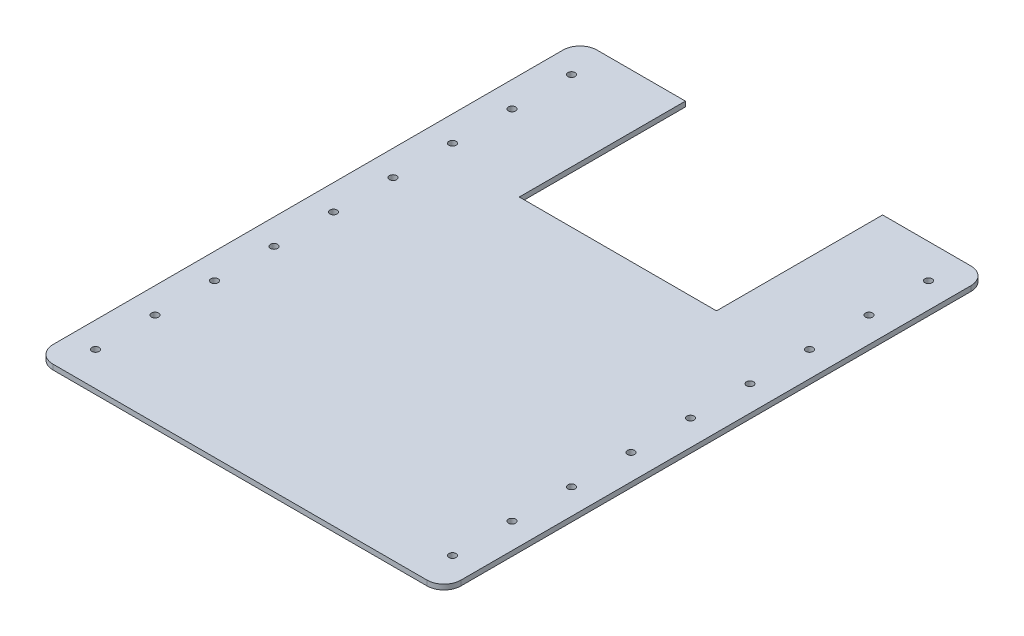
SolidWorks part; units mm, degrees
material "Thornel Mat VMA"
ref_plane "前视基准面" through (0, 0, 0) normal (0, 0, 1) x (1, 0, 0)
ref_plane "上视基准面" through (0, 0, 0) normal (0, 1, 0) x (1, 0, 0)
ref_plane "右视基准面" through (0, 0, 0) normal (1, 0, 0) x (0, 0, -1)
sketch "草图1" plane through (0, 0, 0) normal (0, 1, 0) x (1, 0, 0)
  line L1 (-120, 160) -> (120, 160)
  line L2 (-120, 160) -> (-120, -160)
  line L3 (-120, -160) -> (120, -160)
  line L4 (120, 160) -> (120, -160)
  line L5 (-120, 160) -> (120, -160) construction
  line L6 (-120, -160) -> (120, 160) construction
  point P0 (0, 0)
  dimension "D1" = 320
  dimension "D2" = 240
extrude "凸台-拉伸1" add sketch "草图1" along normal blind 3
fillet "圆角1" radius 10 4 edges at (-120, 1.5, -160) (120, 1.5, -160) (120, 1.5, 160) (-120, 1.5, 160)
sketch "草图2" plane through (0, 3, 0) normal (0, 1, 0) x (1, 0, 0)
  line L0 (-105, -833.0003) -> (-105, 49166.9997) construction
  line L1 (-105, 140) -> (-105, 105) construction
  line L2 (110, 160) -> (-110, 160) construction
  line L3 (0, 0) -> (0, -103.271) construction
  line L4 (105, 140) -> (105, 105) construction
  circle A0 centre (-105, 140) radius 2.1
  circle A1 centre (-105, 105) radius 2.1
  circle A2 centre (-105, 70) radius 2.1
  circle A3 centre (-105, 35) radius 2.1
  circle A4 centre (-105, 0) radius 2.1
  circle A5 centre (-105, -35) radius 2.1
  circle A6 centre (-105, -70) radius 2.1
  circle A7 centre (-105, -105) radius 2.1
  circle A8 centre (-105, -140) radius 2.1
  circle A9 centre (105, -140) radius 2.1
  circle A10 centre (105, -105) radius 2.1
  circle A11 centre (105, -70) radius 2.1
  circle A12 centre (105, -35) radius 2.1
  circle A13 centre (105, 0) radius 2.1
  circle A14 centre (105, 35) radius 2.1
  circle A15 centre (105, 70) radius 2.1
  circle A16 centre (105, 105) radius 2.1
  circle A17 centre (105, 140) radius 2.1
  dimension "D1" = 4.2
  dimension "D2" = 20
  dimension "D3" = 15
  dimension "D5" = 35
  dimension "D4" = 9
extrude "切除-拉伸1" cut sketch "草图2" against normal blind 3
sketch "草图3" plane through (0, 3, 0) normal (0, 1, 0) x (1, 0, 0)
  line L0 (-57.9999, 160) -> (-57.9999, 62.2886)
  line L1 (110, 160) -> (-110, 160) construction
  line L2 (-57.9999, 62.2886) -> (57.9999, 62.2886)
  line L3 (0, 62.2886) -> (0, 170.5278) construction
  line L4 (57.9999, 160) -> (57.9999, 62.2886)
  line L5 (110, 160) -> (-110, 160)
  line M22 (110, 160) -> (-110, 160)
extrude "切除-拉伸2" cut sketch "草图3" against normal blind 10 contours L2 L3 L5 L0 | L3 L2 L4 M22 region at (-28.9999, 3, -111.1443) region at (28.9999, 3, -111.1443)
